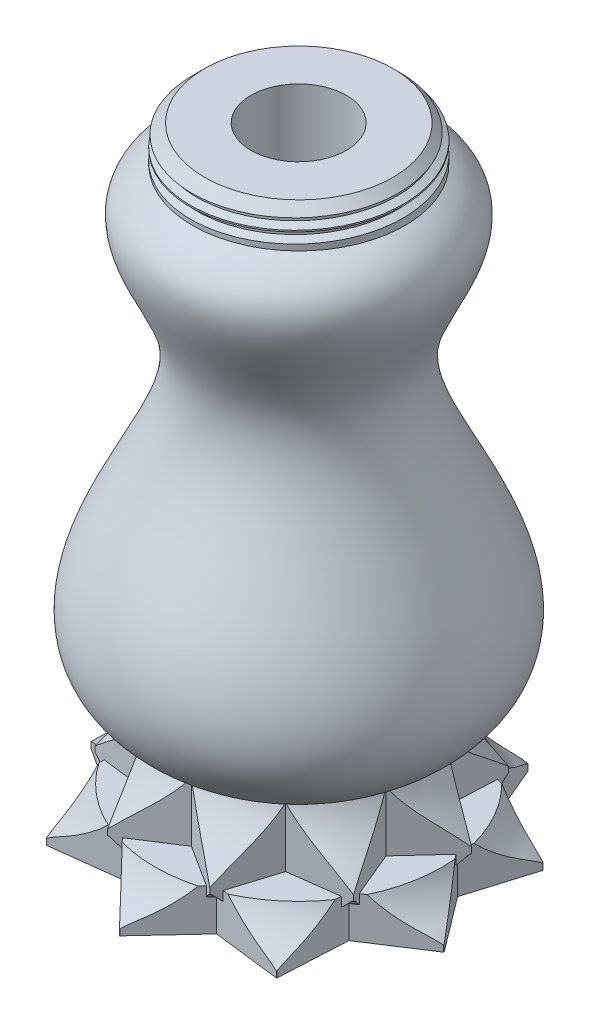
SolidWorks part; units mm, degrees
ref_plane "Front Plane" through (0, 0, 0) normal (0, 0, 1) x (1, 0, 0)
ref_plane "Top Plane" through (0, 0, 0) normal (0, 1, 0) x (1, 0, 0)
ref_plane "Right Plane" through (0, 0, 0) normal (1, 0, 0) x (0, 0, -1)
sketch "Szkic1" plane through (0, 0, 0) normal (0, 1, 0) x (1, 0, 0)
  line L0 (3.9332, -10.8065) -> (-0.2904, -15.3342)
  line L22 (3.9332, -10.8065) -> (10.2152, -11.5706)
  arc A4 (-0.2904, -15.3342) -> (10.2152, -11.5706) centre (0.6329, -1.3671) ccw
  point P37 (0, 0)
sketch "Szkic3" plane through (0, 0, 0) normal (0, 0, 1) x (1, 0, 0)
  line L0 (0, 0) -> (15, 0)
  line L3 (0, 5) -> (0, 0)
  line L4 (15, 0) -> (15, 0.5)
  line L5 (11.5, 5) -> (0, 5)
  spline S0 degree 3 poles (15, 0.5) (14.7029, 0.8071) (13.0949, 1.7546) (11.7809, 3.529) (11.5, 5) knots 0 0 0 0 0.293201 1 1 1 1
  dimension "D1" = 15
  dimension "D2" = 5
  dimension "D3" = 11.5
  dimension "D4" = 0.5
revolve "Obrót1" add sketch "Szkic3" angle 360 about L3
sketch "Szkic7" plane through (0, 0, 0) normal (0, 0, 1) x (1, 0, 0)
  line L1 (0, 0) -> (0, 12.8804)
extrude "Wytnij-wyciągnięcie5" cut sketch "Szkic1" against normal blind 5 and the other way blind 5 contours L0 A4 L22
pattern_circular "Szyk kołowy2" count 9 over 360 about axis through (0, 0, 0) along (0, 1, 0) of "Wytnij-wyciągnięcie5" reverse direction yes
ref_plane "Płaszczyzna1" through (0, 3.5, 0) normal (0, 1, 0) x (1, 0, 0)
sketch "Szkic8" plane through (0, 3.5, 0) normal (0, 1, 0) x (1, 0, 0)
  line L4 (5.7949, -6.8861) -> (4.292, -11.7401)
  line L5 (5.7949, -6.8861) -> (10.8342, -6.2346)
  arc A0 (4.292, -11.7401) -> (10.8342, -6.2346) centre (0, 0) ccw
sketch "Szkic10" plane through (0, 0, 0) normal (0, 0, 1) x (1, 0, 0)
  line L1 (9, 8.5) -> (0, 8.5)
  line L2 (0, 0) -> (0, 12.8804) construction
  line L7 (12.5, 4) -> (12.5, 3.5)
  line L11 (12.5, 3.5) -> (0, 3.5)
  line L12 (0, 3.5) -> (0, 8.5)
  line L13 (10.8342, 3.5) -> (4.292, 3.5) construction
  spline S0 degree 3 poles (12.5, 4) (11.2247, 5.4071) (9.7016, 6.6732) (9, 8.5) knots 0 0 0 0 1 1 1 1
  dimension "D1" = 0.5
  dimension "D2" = 9
  dimension "D3" = 12.5
  dimension "D4" = 0
  dimension "D5" = 5
revolve "Obrót2" add sketch "Szkic10" angle 360 about L12
sweep "Wycięcie-wyciągnięcie po ścieżce1" cut profiles "Szkic8" path "Szkic7"
ref_axis "Oś1" through (0, 8.925, 0) along (0, -1, 0)
pattern_circular "Szyk kołowy3" count 9 over 360 about axis through (0, 8.925, 0) along (0, -1, 0) of "Wycięcie-wyciągnięcie po ścieżce1"
sketch "Szkic11" plane through (0, 0, 0) normal (0, 0, 1) x (1, 0, 0)
  line L0 (0.0128, 8.5) -> (0.0128, 48.5)
  line L2 (8.8655, 8.5) -> (0.0128, 8.5)
  line L3 (8.9128, 48.5004) -> (8.9128, 51.5)
  line L4 (8.9128, 51.5) -> (0.0128, 51.5)
  line L5 (0.0128, 51.5) -> (0.0128, 48.5)
  spline S0 degree 3 poles (8.8655, 8.5) (17.9396, 13.1722) (12.3527, 23.309) (5.6505, 37.441) (14.4989, 45.3737) (8.9128, 48.5004) knots 0 0 0 0 0.470523 0.693516 1 1 1 1
  dimension "D1" = 40
  dimension "D2" = 8.9
  dimension "D3" = 3
revolve "Obrót3" add sketch "Szkic11" angle 360 about L0
chamfer "Sfazowanie1" distance 1 angle 45 1 edges at (0.0128, 51.5, -8.9)
thread "Gwint1" pitch 1 method cut profile "Profil gwintu2" start angle 0, offset 1, length 2, pitch 1, diameter 17.8
ref_plane "Płaszczyzna3" through (-8.8872, 51.5, 0) normal (0, 0, 1) x (-1, 0, 0)
sketch "Profil gwintu2" plane through (-8.8872, 51.5, 0) normal (0, 0, 1) x (-1, 0, 0)
  line L0 (0, 0) -> (0, 1) construction
  line L11 (0, 0) -> (0, 0.875)
  line L12 (0, 0.875) -> (-0.5413, 0.5625)
  line L13 (-0.5413, 0.5625) -> (-0.5413, 0.3125)
  line L15 (-0.5413, 0.3125) -> (0, 0)
  line L17 (-0.5413, 0.4375) -> (0, 0.4375) construction
  point P2 (0, 0)
  dimension "Pitch" = 1
  dimension "Profile_Angle" = 60
  dimension "Profile_Land" = 0.25
  dimension "Profile_Height" = 0.5413
chamfer "Sfazowanie2" distance 0.8 angle 45 18 edges at (-4.2323, 3.5, 10.8431) (-3.7185, 3.5, 11.0362) (-10.212, 3.5, 5.5859) (-9.9425, 3.5, 6.064) (-11.4133, 3.5, -2.2851) (-11.5142, 3.5, -1.7456) (-7.6984, 3.5, -8.7384) (-7.2743, 3.5, -9.0868) (-0.2803, 3.5, -11.6424) (0.2685, 3.5, -11.6367) (7.2689, 3.5, -9.0988) (7.6856, 3.5, -8.7417) (11.4169, 3.5, -2.2978) (11.5066, 3.5, -1.7563) (9.9435, 3.5, 6.0509) (10.2228, 3.5, 5.5784) (3.7277, 3.5, 11.0268) (4.2454, 3.5, 10.8444)
sketch "Szkic12" plane through (0, 51.5, 0) normal (0, 1, 0) x (1, 0, 0)
  circle A0 centre (0, 0) radius 4
  dimension "D1" = 8
extrude "Wytnij-wyciągnięcie6" cut sketch "Szkic12" against normal blind 20
